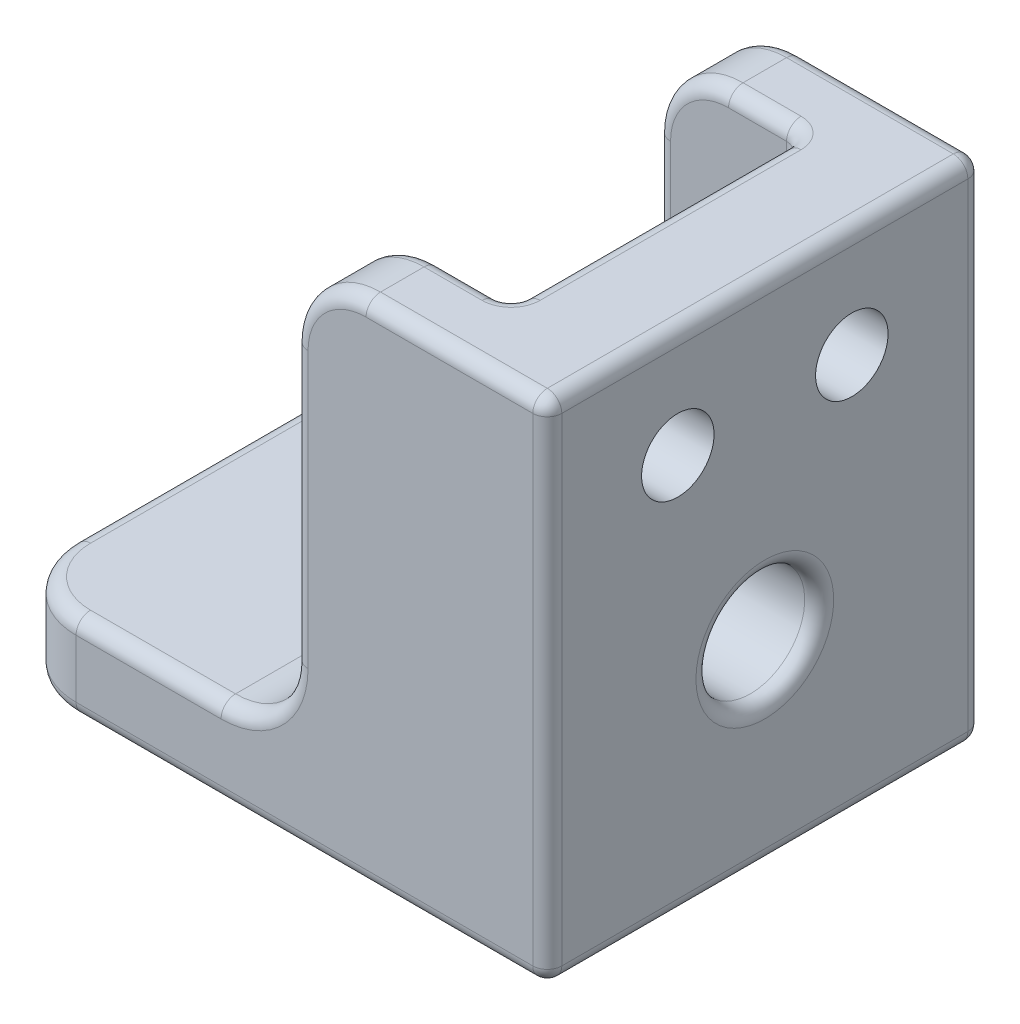
SolidWorks part; units mm, degrees
ref_plane "Front Plane" through (0, 0, 0) normal (0, 0, 1) x (1, 0, 0)
ref_plane "Top Plane" through (0, 0, 0) normal (0, 1, 0) x (1, 0, 0)
ref_plane "Right Plane" through (0, 0, 0) normal (1, 0, 0) x (0, 0, -1)
sketch "Sketch1" plane through (0, 0, 0) normal (0, 1, 0) x (1, 0, 0)
  line L1 (0, 0) -> (15, 0)
  line L2 (0, 0) -> (0, -12)
  line L3 (0, -12) -> (15, -12)
  line L4 (15, 0) -> (15, -12)
  circle A0 centre (6, -6) radius 1.6
  dimension "D4" = 3.2
  dimension "D2" = 15
  dimension "D3" = 6
  dimension "D5" = 6
extrude "Boss-Extrude1" add sketch "Sketch1" along normal blind 2.4
sketch "Sketch3" plane through (0, 2.4, 0) normal (0, 1, 0) x (1, 0, 0)
  line L0 (15, 0) -> (0, 0) construction
  line L1 (15, -12) -> (12, -12)
  line L2 (15, -12) -> (15, 0)
  line L3 (15, 0) -> (12, 0)
  line L4 (12, -12) -> (12, 0)
  line L6 (12, 0) -> (8, 0)
  line L7 (12, 0) -> (12, -2)
  line L8 (12, -2) -> (8, -2)
  line L9 (8, 0) -> (8, -2)
  line L10 (12, -12) -> (8, -12)
  line L11 (12, -12) -> (12, -10)
  line L12 (12, -10) -> (8, -10)
  line L13 (8, -12) -> (8, -10)
  line M7 (0, -12) -> (15, -12)
  line M8 (15, -12) -> (15, 0)
  line M9 (15, 0) -> (0, 0)
  dimension "D1" = 3
  dimension "D2" = 2
  dimension "D3" = 2
  dimension "D4" = 4
  dimension "D5" = 4
extrude "Boss-Extrude2" add sketch "Sketch3" along normal blind 11.6 contours L9 L8 L4 M9 | L4 M7 M8 M9 | L13 L4 L12 M7 region at (13.5, 2.4, 6) region at (10, 2.4, 11) region at (10, 2.4, 1)
sketch "Sketch4" plane through (12, 0, 0) normal (-1, 0, 0) x (0, 0, 1)
  line L0 (10, 2.4) -> (2, 2.4) construction
  line L1 (0, 14) -> (0, 2.4) construction
  line L2 (10, 14) -> (2, 14) construction
  line L3 (2, 14) -> (2, 2.4) construction
  line L4 (10, 14) -> (10, 2.4) construction
  circle A0 centre (6, 5.4) radius 1.5
  circle A1 centre (3.6, 11) radius 1
  circle A2 centre (8.4, 11) radius 1
  dimension "D3" = 6
  dimension "D1" = 3
  dimension "D4" = 2
  dimension "D5" = 2
  dimension "D2" = 3
  dimension "D6" = 3
  dimension "D7" = 3
  dimension "D8" = 1.6
  dimension "D9" = 1.6
extrude "Cut-Extrude1" cut sketch "Sketch4" against normal blind 11.6
fillet "Fillet1" radius 2 6 edges at (8, 2.4, 11) (8, 2.4, 1) (8, 14, 1) (8, 14, 11) (0, 1.2, 0) (0, 1.2, 12)
fillet "Fillet2" radius 0.4 18 edges at (12.5, 14, 0) (8.5858, 13.4142, 0) (8, 8.2, 0) (7.4142, 2.9858, 0) (12.5, 14, 12) (8.5858, 13.4142, 12) (8, 8.2, 12) (7.4142, 2.9858, 12) (0.5858, 2.4, 11.4142) (0, 2.4, 6) (0.5858, 2.4, 0.5858) (4, 2.4, 0) (9, 2.4, 2) (12, 2.4, 6) (9, 2.4, 10) (4, 2.4, 12) (6, 2.4, 7.6) (15, 5.4, 7.5)
fillet "Fillet3" radius 0.4 5 edges at (11.8828, 2.5172, 9.8828) (11.8828, 2.5172, 2.1172) (12, 5.4, 7.5) (12, 8.4, 10) (12, 8.4, 2)
fillet "Fillet4" radius 0.4 2 edges at (12, 11, 9.4) (12, 11, 4.6)
fillet "Fillet5" radius 0.4 12 edges at (15, 6.8, 12) (15, 13.8828, 11.8828) (15, 14, 6) (15, 13.8828, 0.1172) (8.5, 0, 12) (0.5858, 0, 11.4142) (0, 0, 6) (0.5858, 0, 0.5858) (15, 0, 6) (15, 6.8, 0) (6, 0, 7.6) (8.5, 0, 0)
fillet "Fillet6" radius 0.4 13 edges at (6.8833, 2.6056, 9.9496) (7.7889, 3.5056, 10) (8, 8.2, 10) (8.5858, 13.4142, 10) (10.8, 14, 10) (11.8828, 14, 9.8828) (6.8833, 2.6056, 2.0504) (7.7889, 3.5056, 2) (8, 8.2, 2) (8.5858, 13.4142, 2) (10.8, 14, 2) (11.8828, 14, 2.1172) (12, 14, 6)
equation "\"D3@Sketch1\"=\"D1@Sketch1\"/2"
equation "\"D1@Boss-Extrude2\"=14-2.4"
equation "\"D3@Sketch4\"=\"D1@Sketch1\"/2"
equation "\"D9@Sketch4\"=\"D8@Sketch4\""
